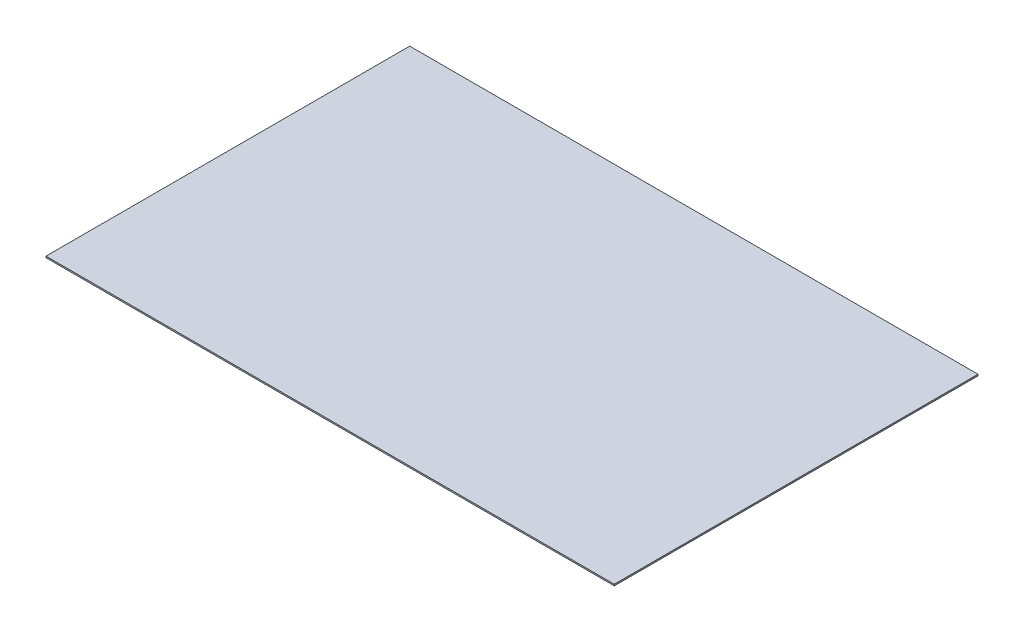
SolidWorks part; units mm, degrees
ref_plane "Front Plane" through (0, 0, 0) normal (0, 0, 1) x (1, 0, 0)
ref_plane "Top Plane" through (0, 0, 0) normal (0, 1, 0) x (1, 0, 0)
ref_plane "Right Plane" through (0, 0, 0) normal (1, 0, 0) x (0, 0, -1)
sketch "Sketch1" plane through (0, 0, 0) normal (0, 1, 0) x (1, 0, 0)
  line L1 (-200, -128) -> (200, -128)
  line L2 (-200, -128) -> (-200, 128)
  line L3 (-200, 128) -> (200, 128)
  line L4 (200, -128) -> (200, 128)
  line L5 (-200, -128) -> (200, 128) construction
  line L6 (-200, 128) -> (200, -128) construction
  point P0 (0, 0)
  dimension "D1" = 400
  dimension "D2" = 256
extrude "Boss-Extrude1" add sketch "Sketch1" along normal blind 1
ref_axis "Middle" through (0, -0.05, 0) along (0, 1, 0)
ref_plane "Plane1" through (0, 0, 52) normal (0, 0, -1) x (-1, 0, 0)
ref_axis "LeftFar" through (200, 1.05, 52) along (0, -1, 0)
ref_axis "RightFar" through (-200, -0.05, 52) along (0, 1, 0)
ref_axis "LeftNear" through (200, 1, -128) along (0, -1, 0)
ref_axis "RightNear" through (-200, 1, -128) along (0, -1, 0)
